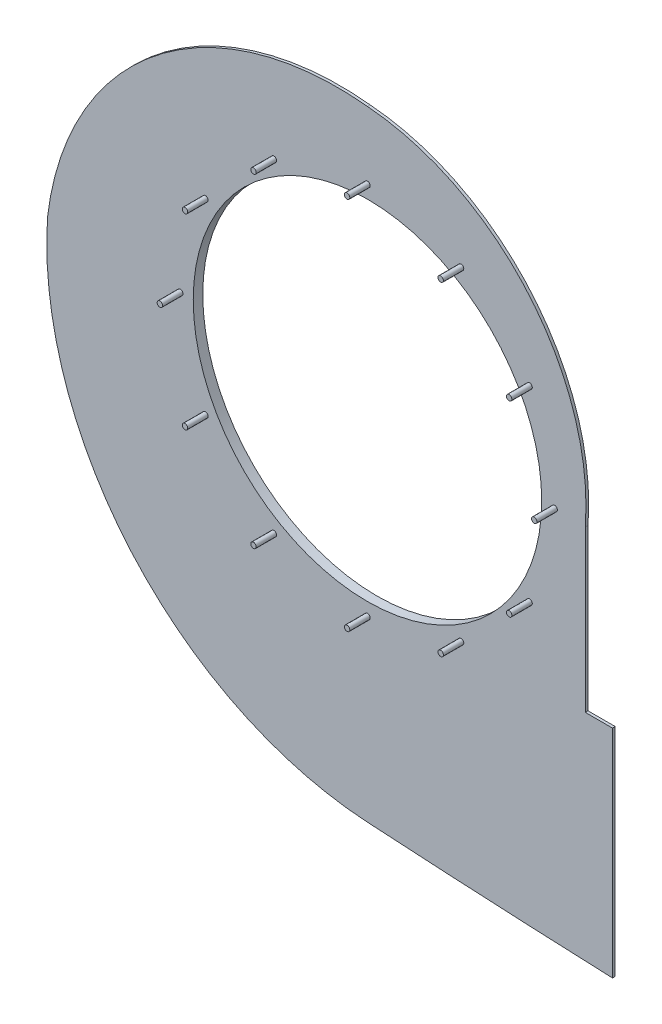
SolidWorks part; units mm, degrees
material "ASTM A36 Steel"
ref_plane "Front Plane" through (0, 0, 0) normal (0, 0, 1) x (1, 0, 0)
ref_plane "Top Plane" through (0, 0, 0) normal (0, 1, 0) x (1, 0, 0)
ref_plane "Right Plane" through (0, 0, 0) normal (1, 0, 0) x (0, 0, -1)
sketch "Sketch1" plane through (0, 0, 0) normal (0, 0, 1) x (1, 0, 0)
  line L0 (60.4241, 203.7442) -> (302.1207, 203.7442) construction
  line L1 (865.2691, 521.0572) -> (865.2691, 757.0572)
  line L2 (865.2691, 521.0572) -> (905.2691, 521.0572)
  line L3 (905.2691, 521.0572) -> (905.2691, 203.0572)
  line L4 (905.2691, 362.0572) -> (1163.8144, 362.0572) construction
  line L5 (1052.4058, 757.0572) -> (545.2691, 757.0572) construction
  line L6 (545.2691, 757.0572) -> (545.2691, 1175.6872) construction
  arc A1 (75.2691, 757.0572) -> (545.2691, 1132.0572) centre (500.9272, 705.599) cw
  arc A2 (545.2691, 221.2717) -> (75.2691, 757.0572) centre (576.0662, 722.3261) cw
  arc A3 (545.2691, 1132.0572) -> (865.2691, 757.0572) centre (517.3547, 784.2035) cw
  arc A4 (545.2691, 221.2717) -> (905.2691, 203.0572) centre (1565.8135, 16825.0409) ccw
  dimension "D1" = 40
  dimension "D9" = 502
  dimension "D2" = 320
  dimension "D3" = 470
  dimension "D4" = 375
  dimension "D5" = 395
  dimension "D6" = 318
extrude "Boss-Extrude1" add sketch "Sketch1" along normal blind 4
sketch "Sketch2" plane through (0, 0, 4) normal (0, 0, 1) x (1, 0, 0)
  line L0 (865.2691, 521.0572) -> (865.2691, 757.0572) construction
  circle A0 centre (545.2691, 758.0572) radius 256
  dimension "D1" = 512
  dimension "D2" = 374
  dimension "D3" = 320
extrude "Cut-Extrude1" cut sketch "Sketch2" against normal blind 4
sketch "Sketch3" plane through (0, 0, 0) normal (0, 0, -1) x (-1, 0, 0)
  circle A0 centre (-545.2691, 758.0572) radius 256
extrude "Extrude-Thin1" add sketch "Sketch3" along normal blind 10 thin thin type one direction wall 2
sketch "Sketch5" plane through (0, 0, 4) normal (0, 0, 1) x (1, 0, 0)
  line L1 (545.2691, 758.0572) -> (545.2691, 1033.0572) construction
  circle A0 centre (545.2691, 1033.0572) radius 4
  circle A1 centre (545.2691, 758.0572) radius 256 construction
  point P6 (545.2691, 758.0572)
  dimension "D1" = 8
  dimension "D2" = 275
extrude "Boss-Extrude2" add sketch "Sketch5" along normal blind 30
pattern_circular "CirPattern1" count 12 every 30 about axis through (545.2691, 758.0572, 4) along (0, 0, 1) of "Boss-Extrude2"
